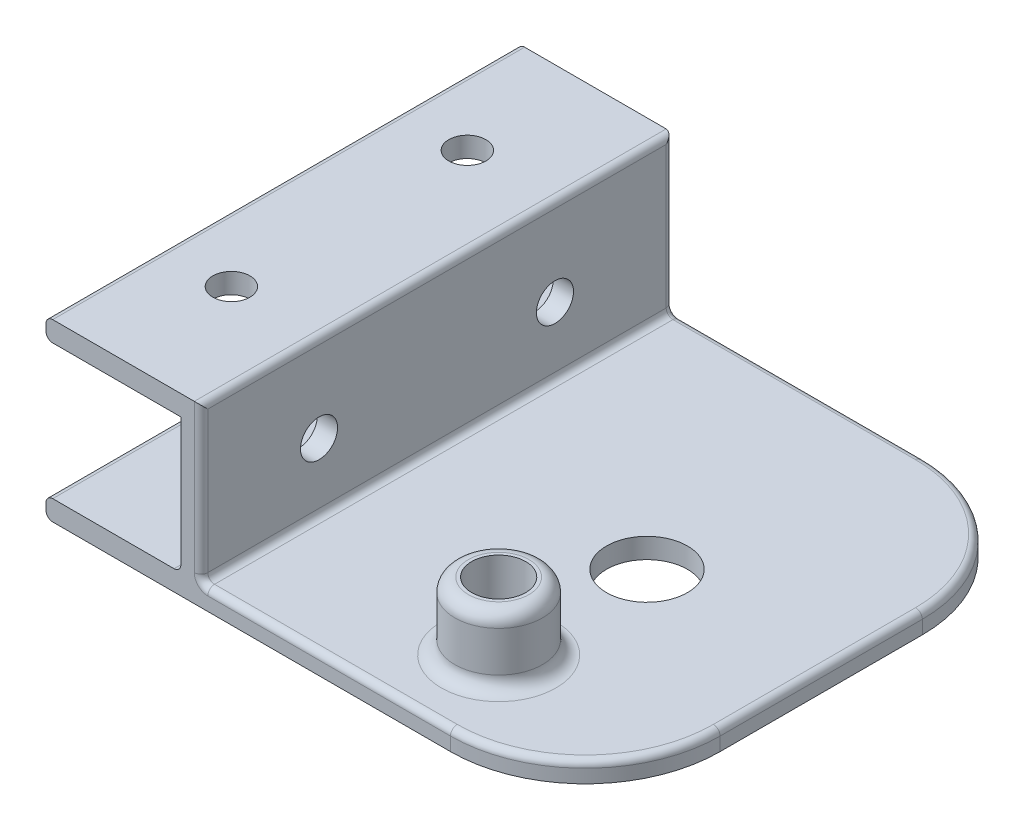
SolidWorks part; units mm, degrees
note: The reader was unsure of these and kept them because the rebuilt part matched: shared geometry of "Sketch1<3>", "Sketch1<4>", "Sketch3<4>".
ref_plane "Front Plane" through (0, 0, 0) normal (0, 0, 1) x (1, 0, 0)
ref_plane "Top Plane" through (0, 0, 0) normal (0, 1, 0) x (1, 0, 0)
ref_plane "Right Plane" through (0, 0, 0) normal (1, 0, 0) x (0, 0, -1)
sketch "Sketch1" plane through (0, 0, 0) normal (0, 1, 0) x (1, 0, 0)
  line L1 (-40, -35) -> (40, -35)
  line L2 (-40, -35) -> (-40, 35)
  line L3 (-40, 35) -> (40, 35)
  line L4 (40, -35) -> (40, 35)
  line L5 (-40, -35) -> (40, 35) construction
  line L6 (-40, 35) -> (40, -35) construction
  line L7 (-20, 35) -> (-17, 35)
  line L8 (-20, 35) -> (-20, -35)
  line L9 (-20, -35) -> (-17, -35)
  line L10 (-17, 35) -> (-17, -35)
  circle A0 centre (-30, 17.5) radius 2.5
  circle A1 centre (-30, -17.5) radius 2.5
  point P0 (0, 0)
  dimension "D7" = 5
  dimension "D8" = 5
  dimension "D1" = 80
  dimension "D2" = 70
  dimension "D3" = 17.5
  dimension "D4" = 17.5
  dimension "D5" = 10
  dimension "D6" = 10
  dimension "D9" = 20
  dimension "D10" = 3
extrude "Boss-Extrude1" add sketch "Sketch1" along normal blind 3 contours L8 L3 L2 L1 A1 A0 | L3 L10 L1 L4 | L10 L3 L8 L1
extrude "Boss-Extrude2" add sketch "Sketch1<3>" along normal blind 26 contours L10 L3 L8 L1
sketch "Sketch1<3>" plane through (0, 0, 0) normal (0, 1, 0) x (1, 0, 0) same geometry as "Sketch1"
sketch "Sketch2" plane through (-17, 0, 0) normal (1, 0, 0) x (0, 0, -1)
  line L0 (-35, 3) -> (-35, 23)
  line L1 (-35, 26) -> (-35, 3) construction
  line L2 (-35, 23) -> (35, 23)
  line L3 (35, 26) -> (35, 3) construction
  line L4 (35, 23) -> (35, 3)
  line L5 (35, 3) -> (-35, 3)
  circle A0 centre (-17.5, 13) radius 2.5
  circle A1 centre (17.5, 13) radius 2.5
  point P9 (0, 3)
  point P15 (-35, 13)
  point P17 (17.5, 13)
  point P18 (-17.5, 13)
  dimension "D4" = 5
  dimension "D5" = 5
  dimension "D1" = 17.5
  dimension "D2" = 17.5
  dimension "D3" = 20
sketch "Sketch3" plane through (0, 3, 0) normal (0, 1, 0) x (1, 0, 0)
  line L0 (-17, -35) -> (-17, 35) construction
  line L1 (-7, -21.15) -> (35.3, -21.15)
  line L2 (-7, -21.15) -> (-7, 21.15)
  line L3 (-7, 21.15) -> (35.3, 21.15)
  line L4 (35.3, -21.15) -> (35.3, 21.15)
  line L5 (-7, -21.15) -> (35.3, 21.15) construction
  line L6 (-7, 21.15) -> (35.3, -21.15) construction
  line L7 (-7, 0) -> (35.3, 0) construction
  line L8 (14.15, 21.15) -> (14.15, -21.15) construction
  circle A3 centre (14.15, 0) radius 11.0045
  circle A4 centre (29.65, 15.5) radius 1.5
  circle A5 centre (-1.35, 15.5) radius 1.5
  circle A6 centre (-1.35, -15.5) radius 1.5
  circle A7 centre (29.65, -15.5) radius 1.5
  circle A8 centre (14.15, 0) radius 12.5
  circle A9 centre (14.15, 0) radius 6
  point P11 (-7, 0)
  point P14 (-17, 0)
  dimension "D7" = 3
  dimension "D11" = 3
  dimension "D12" = 3
  dimension "D13" = 3
  dimension "D14" = 22.009
  dimension "D15" = 25
  dimension "D16" = 12
  dimension "D2" = 31
  dimension "D3" = 31
  dimension "D4" = 0
  dimension "D5" = 31
  dimension "D6" = 31
  dimension "D8" = 42.3
  dimension "D9" = 42.3
  dimension "D10" = 10
extrude "Cut-Extrude2" cut sketch "Sketch3" against normal blind 10 contours A3 | A9
fillet "Fillet1" radius 20 2 edges at (40, 1.5, 35) (40, 1.5, -35)
extrude "Boss-Extrude4" add sketch "Sketch1<4>" against normal blind 3 from surface at 26 contours L8 L3 L2 L1 A1 A0 starting at face at (-18.5, 26, 0)
sketch "Sketch1<4>" plane through (0, 0, 0) normal (0, 1, 0) x (1, 0, 0) same geometry as "Sketch1"
sketch "Sketch4" plane through (0, 3, 0) normal (0, 1, 0) x (1, 0, 0)
  circle A0 centre (14.15, -22) radius 4
  circle A1 centre (14.15, -22) radius 6.5
  point P5 (14.15, 0)
  dimension "D1" = 8
  dimension "D2" = 13
  dimension "D3" = 22
extrude "Boss-Extrude5" add sketch "Sketch4" along normal blind 10
fillet "Fillet2" radius 1 12 edges at (-20, 3, 0) (-17, 14.5, 35) (-17, 3, 0) (-17, 26, 0) (-17, 14.5, -35) (-40, 3, 0) (40, 3, 0) (34.1421, 3, -29.1421) (34.1421, 3, 29.1421) (-40, 23, 0) (-40, 26, 0) (-40, 0, 0)
extrude "Boss-Extrude7" add sketch "Sketch3<4>" against normal up to surface (3 mm away) contours A3 A9 up to face at (14.15, 0, 11.0045)
sketch "Sketch3<4>" plane through (0, 3, 0) normal (0, 1, 0) x (1, 0, 0) same geometry as "Sketch3"
fillet "Fillet3" radius 2 2 edges at (14.15, 13, 28.5) (14.15, 3, 28.5)
hole_wizard "M5 Clearance Hole1" positions "Sketch5" profile "Sketch6" hole size "M5" standard "ANSI Metric"
sketch "Sketch5" plane through (-17, 0, 0) normal (1, 0, 0) x (0, 0, -1)
  point P0 (-17.5, 13)
  point P3 (17.5, 13)
sketch "Sketch6" plane through (-17, 13, 17.5) normal (0, 1, 0) x (0, 0, -1)
  line L0 (0, 0) -> (0, 23)
  line L1 (0, 23) -> (2.75, 23)
  line L2 (2.75, 23) -> (2.75, 0)
  line L5 (2.75, 0) -> (0, 0)
  line L11 (0, -6.35) -> (0, 107.95) construction
  dimension "Thru Hole Dia." = 5.5
  dimension "Thru Hole Depth" = 23
hole_wizard "M5 Clearance Hole2" positions "Sketch7" profile "Sketch8" hole size "M5" standard "ANSI Metric" end condition through all
sketch "Sketch7" plane through (0, 26, 0) normal (0, 1, 0) x (1, 0, 0)
  point P0 (-30, -17.5)
  point P3 (-30, 17.5)
sketch "Sketch8" plane through (-30, 26, 17.5) normal (1, 0, 0) x (0, 0, 1)
  line L0 (0, 0) -> (0, 26)
  line L1 (0, 26) -> (2.75, 26)
  line L2 (2.75, 26) -> (2.75, 0)
  line L5 (2.75, 0) -> (0, 0)
  line L11 (0, -6.35) -> (0, 107.95) construction
  dimension "Thru Hole Dia." = 5.5
  dimension "Thru Hole Depth" = 26
